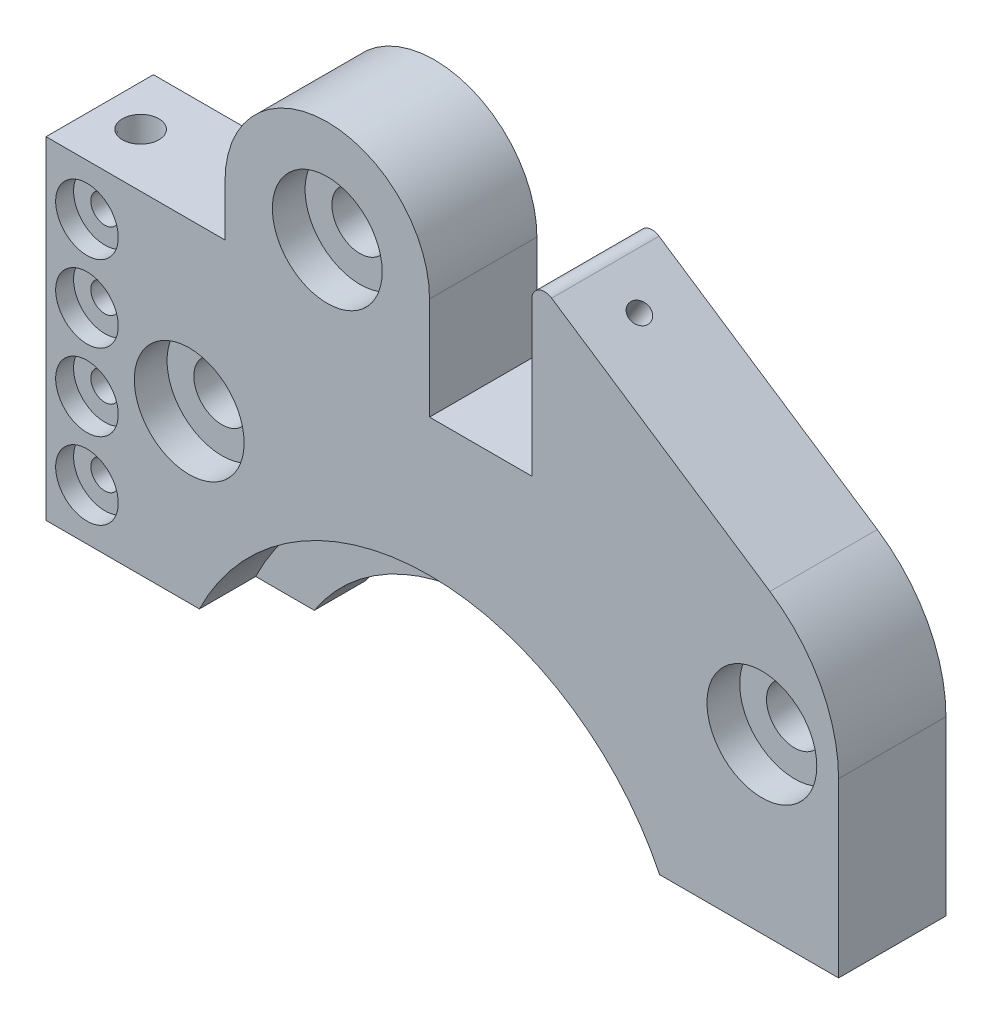
SolidWorks part; units mm, degrees
ref_plane "Front Plane" through (0, 0, 0) normal (0, 0, 1) x (1, 0, 0)
ref_plane "Top Plane" through (0, 0, 0) normal (0, 1, 0) x (1, 0, 0)
ref_plane "Right Plane" through (0, 0, 0) normal (1, 0, 0) x (0, 0, -1)
sketch "Sketch1" plane through (0, 0, 0) normal (0, 0, 1) x (1, 0, 0)
  line L0 (35, 65) -> (0, 65)
  line L1 (0, 65) -> (0, 0)
  line L2 (0, 0) -> (30, 0)
  line L3 (30, 0) -> (120, 0) construction
  line L4 (120, 0) -> (155, 0)
  line L5 (155, 0) -> (155, 33.7586)
  line L6 (141.5831, 58.7586) -> (98.8819, 87.0833)
  line L7 (95, 85) -> (95, 55)
  line L8 (95, 55) -> (75, 55)
  line L9 (75, 55) -> (75, 75)
  line L11 (35, 75) -> (35, 65)
  line L12 (75, -21.7945) -> (75, 40.8014) construction
  line L13 (0, 32.5) -> (43.179, 32.5) construction
  arc A0 (30, 0) -> (120, 0) centre (75, -21.7945) cw
  arc A1 (41.459, 0) -> (108.541, 0) centre (75, -21.7945) cw construction
  arc A2 (35, 75) -> (75, 75) centre (55, 75) cw
  arc A3 (155, 33.7586) -> (141.5831, 58.7586) centre (125, 33.7586) ccw
  arc A4 (98.8819, 87.0833) -> (95, 85) centre (97.5, 85) ccw
  arc A5 (39, -4.3589) -> (111, -4.3589) centre (75, -21.7945) cw construction
  circle A6 centre (8, 10) radius 5 construction
  circle A7 centre (8, 25) radius 5 construction
  circle A8 centre (8, 40) radius 5 construction
  circle A9 centre (8, 55) radius 5 construction
  circle A10 centre (28, 32.5) radius 10 construction
  circle A11 centre (140, 33.7586) radius 7.5 construction
  point P17 (75, 28.2055)
  point P23 (75, 9.5034)
  point P39 (0, 0)
  dimension "D1" = 30
  dimension "D2" = 2.5
  dimension "D4" = 20
  dimension "D5" = 50
  dimension "D6" = 45
  dimension "D13" = 10
  dimension "D17" = 10
  dimension "D21" = 20
  dimension "D23" = 15
  dimension "D3" = 65
  dimension "D7" = 30
  dimension "D8" = 35
  dimension "D9" = 10
  dimension "D10" = 20
  dimension "D11" = 30
  dimension "D12" = 20
  dimension "D14" = 35
  dimension "D15" = 25
  dimension "D16" = 10
  dimension "D18" = 8
  dimension "D20" = 15
  dimension "D22" = 28
  dimension "D24" = 15
  dimension "D19" = 4
extrude "Boss-Extrude1" add sketch "Sketch1" along normal blind 21
sketch "Sketch2" plane through (0, 0, 0) normal (0, 0, 1) x (1, 0, 0)
  line L0 (30, 0) -> (41.459, 0)
  line L1 (108.541, 0) -> (120, 0)
  arc A0 (108.541, 0) -> (41.459, 0) centre (75, -21.7945) ccw construction
  arc A1 (108.541, 0) -> (41.459, 0) centre (75, -21.7945) ccw
  arc A2 (120, 0) -> (30, 0) centre (75, -21.7945) ccw construction
  arc A3 (120, 0) -> (30, 0) centre (75, -21.7945) ccw
extrude "Boss-Extrude2" add sketch "Sketch2" along normal blind 10
sketch "Sketch8" plane through (0, 65, 0) normal (0, 1, 0) x (1, 0, 0)
  line L0 (0, -21) -> (0, 0) construction
  line L1 (0, -10.5) -> (24.3066, -10.5) construction
  circle A0 centre (8, -10.5) radius 2.5 construction
  point P6 (0, 0)
  point P7 (0, 0)
  dimension "D2" = 5
  dimension "D1" = 8
hole_wizard "1/16 Rc Tapped Hole1" positions "Sketch15" profile "Sketch16" size "1/16" standard "ISO" end condition up to next
sketch "Sketch15" plane through (0, 65, 0) normal (0, 1, 0) x (1, 0, 0)
  point P0 (8, -10.5)
  point P3 (8, -10.5)
sketch "Sketch16" plane through (8, 65, 10.5) normal (1, 0, 0) x (0, 0, 1)
  line L0 (0, 0) -> (0, 65)
  line L1 (0, 65) -> (3.05, 65)
  line L2 (-3.34, 7.4) -> (-3.571, 0) construction
  line L3 (3.05, 65) -> (3.05, 7.4)
  line L4 (3.05, 7.4) -> (3.34, 7.4)
  line L5 (3.34, 7.4) -> (3.571, 0)
  line L7 (3.571, 0) -> (0, 0)
  line L8 (0, -6.35) -> (0, 107.95) construction
  line L11 (-3.05, 7.4) -> (-3.34, 7.4) construction
  dimension "Thru Tap Drill Dia." = 6.1
  dimension "Thru Tap Drill Depth" = 65
  dimension "Thread Dia." = 7.142
  dimension "Thread Angle" = 3.576
  dimension "Thread Depth" = 7.4
cosmetic thread "Hole Thread1" parameters "D1"=7.4, "D2"=7.723
hole_wizard "CBORE for M5 Hex Head Bolt1" positions "Sketch3" profile "Sketch4" counterbore size "M5" standard "ISO" end condition up to next
sketch "Sketch3" plane through (0, 0, 21) normal (0, 0, 1) x (1, 0, 0)
  point P0 (8, 55)
  point P3 (8, 40)
  point P6 (8, 25)
  point P9 (8, 10)
sketch "Sketch4" plane through (8, 55, 21) normal (1, 0, 0) x (0, -1, 0)
  line L0 (0, 0) -> (0, 7.45)
  line L1 (0, 7.45) -> (2.75, 7.45)
  line L3 (2.75, 7.45) -> (2.75, 3.5)
  line L4 (2.75, 3.5) -> (6.119, 3.5)
  line L5 (6.119, 3.5) -> (6.119, 0)
  line L7 (6.119, 0) -> (0, 0)
  line L11 (0, -6.35) -> (0, 107.95) construction
  dimension "Thru Hole Dia." = 5.5
  dimension "Thru Hole Depth" = 7.45
  dimension "C'Bore Dia." = 12.238
  dimension "C'Bore Depth" = 3.5
hole_wizard "CBORE for M10 Hex Head Bolt1" positions "Sketch5" profile "Sketch6" counterbore size "M10" standard "ISO" end condition up to next
sketch "Sketch5" plane through (0, 0, 21) normal (0, 0, 1) x (1, 0, 0)
  point P0 (28, 32.5)
  point P3 (55, 75)
  point P6 (140, 33.7586)
sketch "Sketch6" plane through (28, 32.5, 21) normal (1, 0, 0) x (0, -1, 0)
  line L0 (0, 0) -> (0, 21)
  line L1 (0, 21) -> (5.5, 21)
  line L3 (5.5, 21) -> (5.5, 6.4)
  line L4 (5.5, 6.4) -> (10.7375, 6.4)
  line L5 (10.7375, 6.4) -> (10.7375, 0)
  line L7 (10.7375, 0) -> (0, 0)
  line L11 (0, -6.35) -> (0, 107.95) construction
  dimension "Thru Hole Dia." = 11
  dimension "Thru Hole Depth" = 21
  dimension "C'Bore Dia." = 21.475
  dimension "C'Bore Depth" = 6.4
sketch "Sketch11" plane through (70.3282, 106.0237, 0) normal (0.5528, 0.8333, 0) x (0.8333, -0.5528, 0)
  line L0 (34.2645, -10.5) -> (85.5059, -10.5) construction
  line L1 (34.2645, -21) -> (34.2645, 0) construction
  line L2 (85.5059, -21) -> (85.5059, 0) construction
  circle A0 centre (42.2645, -10.5) radius 2 construction
  dimension "D1" = 4
  dimension "D2" = 8
hole_wizard "Ø4.0mm Dowel Hole1" positions "Sketch12" profile "Sketch14" hole size "Ø4.0" standard "ISO"
sketch "Sketch12" plane through (70.3282, 106.0237, 0) normal (0.5528, 0.8333, 0) x (0.8333, -0.5528, 0)
  point P0 (42.2645, -10.5)
sketch "Sketch14" plane through (105.5486, 82.6612, 10.5) normal (0, 0, 1) x (-0.8333, 0.5528, 0)
  line L0 (0, 0) -> (0, 11.2017)
  line L1 (0, 11.2017) -> (2, 10)
  line L2 (2, 10) -> (2, 0)
  line L5 (2, 0) -> (0, 0)
  line L10 (0, 11.2017) -> (-2, 10) construction
  line L11 (0, -6.35) -> (0, 107.95) construction
  dimension "Hole Dia." = 4
  dimension "Hole Depth" = 10
  dimension "Drill Angle" = 118
